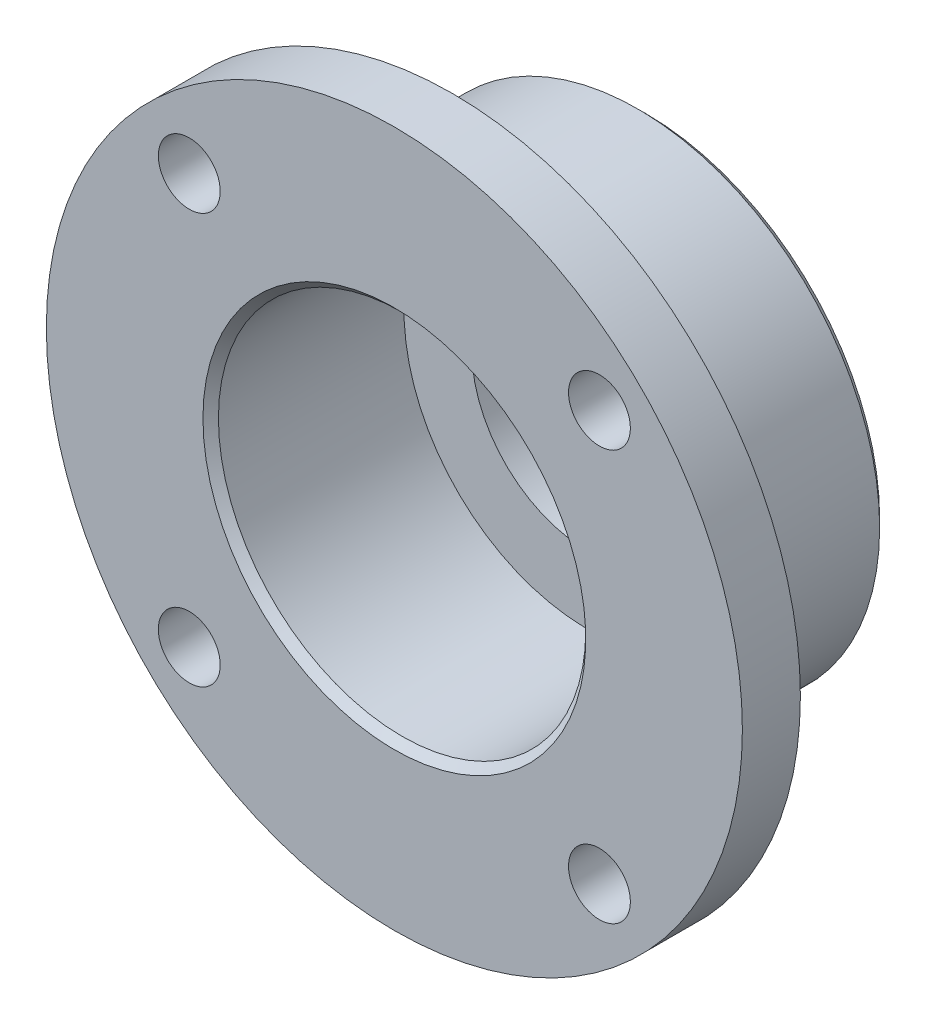
SolidWorks part; units mm, degrees
material "2024 Сплав"
ref_plane "Спереди" through (0, 0, 0) normal (0, 0, 1) x (1, 0, 0)
ref_plane "Сверху" through (0, 0, 0) normal (0, 1, 0) x (1, 0, 0)
ref_plane "Справа" through (0, 0, 0) normal (1, 0, 0) x (0, 0, -1)
sketch "Эскиз1" plane through (0, 0, 0) normal (0, 1, 0) x (1, 0, 0)
  line L0 (-18, 0) -> (-18, 3)
  line L1 (-18, 3) -> (-12.5, 3)
  line L2 (-12.5, 3) -> (-12.5, 13)
  line L3 (-12.5, 13) -> (-6, 13)
  line L4 (-6, 13) -> (-6, 10)
  line L6 (-9.5, 10) -> (-9.5, 0)
  line L7 (-9.5, 0) -> (-18, 0)
  line L8 (0, 0) -> (0, 50000) construction
  line L12 (-9.5, 10) -> (-6, 10)
  point P9 (-7.5, 10)
  point P11 (-7.5, 10.1476)
  dimension "D1" = 6
  dimension "D2" = 12.5
  dimension "D3" = 9.5
  dimension "D4" = 3
  dimension "D5" = 3
  dimension "D6" = 18
  dimension "D7" = 13
revolve "Повернуть1" add sketch "Эскиз1" angle 360 about L8
sketch "Эскиз2" plane through (0, 0, 0) normal (0, 0, 1) x (1, 0, 0)
  line L0 (0, 0) -> (18, 0) construction
  circle A2 centre (0, 0) radius 9.5 construction
  circle A3 centre (10.6066, 10.6066) radius 1.6
  circle A4 centre (0, 0) radius 18 construction
  dimension "D1" = 15
  dimension "D2" = 3.2
  dimension "D3" = 45
extrude "Вырез-Вытянуть1" cut sketch "Эскиз2" against normal up to next
pattern_circular "Круговой массив1" count 4 over 360 about axis through (0, 0, 0) along (0, 0, 1) of "Вырез-Вытянуть1" reverse direction yes
chamfer "Фаска1" distance 0.4 angle 45 2 edges at (12.5, 0, -13) (9.5, 0, 0)
